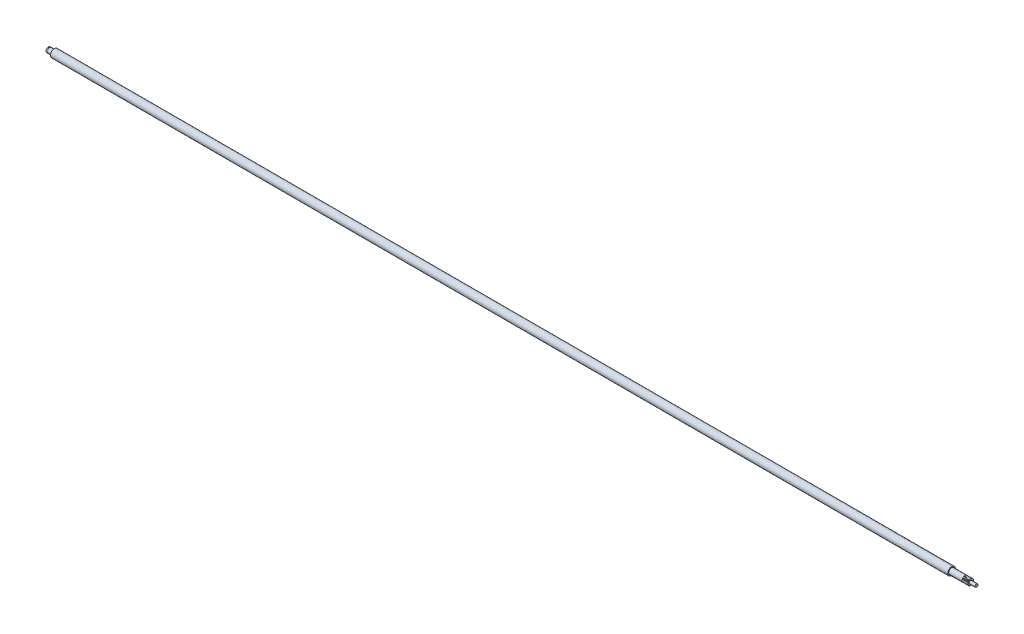
SolidWorks part; units mm, degrees
material "Хромистая нержавеющая сталь"
ref_plane "Спереди" through (0, 0, 0) normal (0, 0, 1) x (1, 0, 0)
ref_plane "Сверху" through (0, 0, 0) normal (0, 1, 0) x (1, 0, 0)
ref_plane "Справа" through (0, 0, 0) normal (1, 0, 0) x (0, 0, -1)
sketch "Эскиз1" plane through (0, 0, 0) normal (0, 0, 1) x (1, 0, 0)
  line L0 (-1813.0019, 5.9419) -> (-1813.0019, 10.9419)
  line L1 (-1813.0019, 10.9419) -> (-1811.3019, 10.9419)
  line L2 (-1811.3019, 10.9419) -> (-1811.3019, 10.7419)
  line L3 (-1811.3019, 10.7419) -> (-1810.1519, 10.7419)
  line L4 (-1810.1519, 10.7419) -> (-1810.1519, 10.9419)
  line L5 (-1810.1519, 10.9419) -> (-1801.0019, 10.9419)
  line L6 (-1801.0019, 10.9419) -> (-1801.0019, 13.9419)
  line L7 (-1801.0019, 13.9419) -> (35.9981, 13.9419)
  line L8 (35.9981, 13.9419) -> (35.9981, 11.9419)
  line L9 (35.9981, 11.9419) -> (74.9981, 11.9419)
  line L10 (74.9981, 11.9419) -> (74.9981, 8.9419)
  line L11 (74.9981, 8.9419) -> (86.9981, 8.9419)
  line L12 (86.9981, 8.9419) -> (86.9981, 5.9419)
  line L13 (86.9981, 5.9419) -> (-1813.0019, 5.9419)
  line L14 (62.9981, 14.6846) -> (62.9981, -1.3142) construction
  dimension "D1" = 1.15
  dimension "D2" = 9.15
  dimension "D3" = 12
  dimension "D4" = 39
  dimension "D5" = 51
  dimension "D6" = 12
  dimension "D7" = 3
  dimension "D8" = 3
  dimension "D9" = 2
  dimension "D10" = 5
  dimension "D11" = 4.8
  dimension "D12" = 5
  dimension "D13" = 1900
revolve "Повернуть1" add sketch "Эскиз1" angle 360 about L13
ref_plane "Плоскость1" through (45.9981, 0, 0) normal (1, 0, 0) x (0, 0, -1)
sketch "Эскиз2" plane through (45.9981, 0, 0) normal (1, 0, 0) x (0, 0, -1)
  circle A0 centre (0, 5.9419) radius 8 construction
  circle A1 centre (0, 5.9419) radius 8
curve "Спираль1" pitch 5 height 290 turns 58
sketch "Эскиз3" plane through (0, 0, 0) normal (0, 0, 1) x (1, 0, 0)
  line L0 (-207.8405, -2.5666) -> (-201.4949, -2.5666) construction
  line L1 (-210.2778, -2.0666) -> (-203.5838, -2.0666) construction
  line L2 (-207.8405, -4.8575) -> (-207.8405, -1.8666) construction
  line L3 (-205.3405, -4.8575) -> (-205.3405, -0.2923) construction
  line L4 (-205.3405, -1.8666) -> (-205.4905, -2.0666)
  line L5 (-205.4905, -2.0666) -> (-205.4905, -2.5666)
  line L6 (-205.4905, -2.5666) -> (-205.1905, -2.5666)
  line L7 (-205.1905, -2.5666) -> (-205.1905, -2.0666)
  line L8 (-205.1905, -2.0666) -> (-205.3405, -1.8666)
  circle A0 centre (-207.8405, -2.5666) radius 1.5875
  point P7 (-207.7498, -2.0666)
  dimension "D1" = 3.175
  dimension "D2" = 0.5
  dimension "D3" = 2.5
  dimension "D4" = 0.2
  dimension "D5" = 0.3
ref_plane "Плоскость2" through (84.9981, 0, 0) normal (1, 0, 0) x (0, 0, -1)
sketch "Эскиз4" plane through (84.9981, 0, 0) normal (1, 0, 0) x (0, 0, -1)
  circle A0 centre (0, 5.9419) radius 6 construction
  circle A1 centre (0, 5.9419) radius 6
curve "Спираль2" pitch 1 height 22 radius 6 centre (84.9981, 5.9419, 0) axis (-1, 0, 0) start towards (0, 0, 1)
sketch "Эскиз5" plane through (0, 0, 0) normal (0, 0, 1) x (1, 0, 0)
  line L0 (76.2561, 0.4419) -> (75.7561, -0.0581)
  line L1 (35.9981, -0.0581) -> (74.9981, -0.0581) construction
  line L2 (75.7561, -0.0581) -> (75.7561, -1.0581)
  line L3 (75.7561, -1.0581) -> (76.7561, -1.0581)
  line L4 (76.7561, -1.0581) -> (76.7561, -0.0581)
  line L5 (76.7561, -0.0581) -> (76.2561, 0.4419)
  line L6 (76.2561, 0.4419) -> (76.2561, -0.2584) construction
  line L7 (75.7561, -0.0581) -> (76.7561, -0.0581) construction
  dimension "D1" = 0.5
  dimension "D2" = 1
  dimension "D3" = 1
sweep "Вырез-По траектории7" cut profiles "Эскиз5" path "Спираль2"
